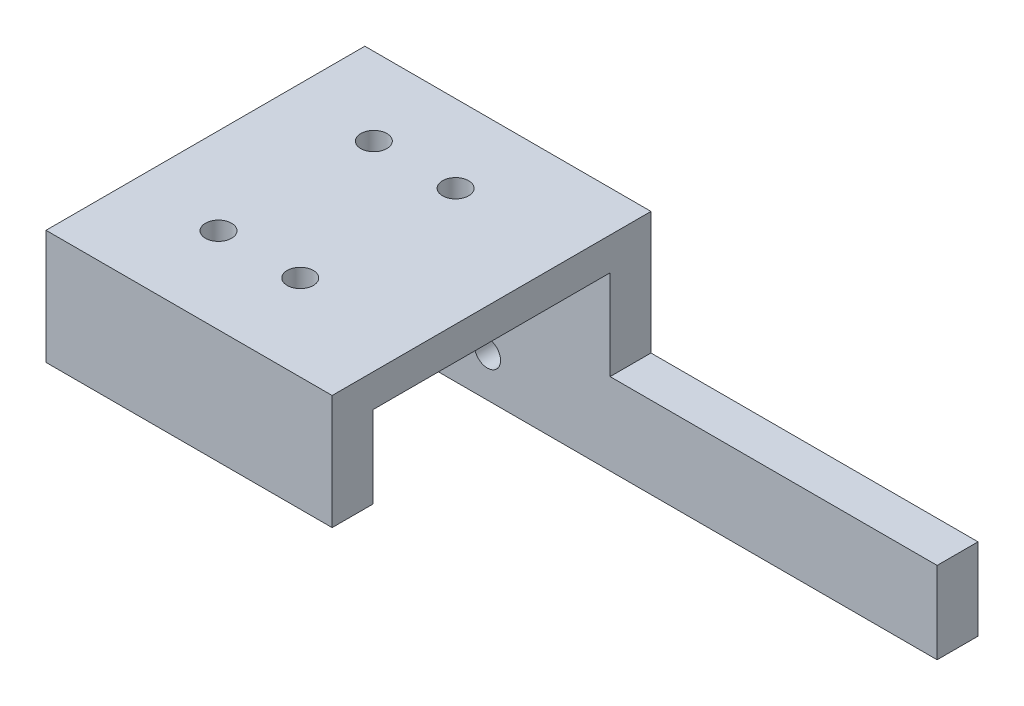
SolidWorks part; units mm, degrees
ref_plane "前视基准面" through (0, 0, 0) normal (0, 0, 1) x (1, 0, 0)
ref_plane "上视基准面" through (0, 0, 0) normal (0, 1, 0) x (1, 0, 0)
ref_plane "右视基准面" through (0, 0, 0) normal (1, 0, 0) x (0, 0, -1)
sketch "草图1" plane through (0, 0, 0) normal (0, 1, 0) x (1, 0, 0)
  line L1 (0, 0) -> (35, 0)
  line L2 (0, 0) -> (0, 39)
  line L3 (0, 39) -> (35, 39)
  line L4 (35, 0) -> (35, 39)
  dimension "D1" = 39
  dimension "D2" = 35
extrude "凸台-拉伸1" add sketch "草图1" along normal blind 4
sketch "草图2" plane through (0, 4, 0) normal (0, 1, 0) x (1, 0, 0)
  line L1 (0, 0) -> (35, 0) construction
  line L3 (0, 20) -> (35, 20) construction
  line L4 (0, 39) -> (0, 0) construction
  circle A0 centre (10.6, 29.5) radius 1.6
  circle A1 centre (20.6, 29.5) radius 1.6
  circle A2 centre (20.6, 10.5) radius 1.6
  circle A3 centre (10.6, 10.5) radius 1.6
  dimension "D3" = 3.2
  dimension "D1" = 10.6
  dimension "D2" = 9.5
  dimension "D4" = 10
  dimension "D5" = 20
extrude "切除-拉伸1" cut sketch "草图2" against normal blind 6
sketch "草图3" plane through (0, 0, 0) normal (0, -1, 0) x (1, 0, 0)
  line L11 (0, -39) -> (35, -39)
  line L12 (0, -39) -> (0, -34)
  line L13 (0, -34) -> (35, -34)
  line L14 (35, -39) -> (35, -34)
  dimension "D1" = 5
  dimension "D2" = 35
extrude "凸台-拉伸2" add sketch "草图3" along normal blind 21
sketch "草图4" plane through (0, 0, -39) normal (0, 0, -1) x (-1, 0, 0)
  line L1 (0, -21) -> (-35, -21) construction
  line L2 (0, 4) -> (0, -21) construction
  circle A0 centre (-10, -16) radius 1.6
  circle A1 centre (-20, -16) radius 1.6
  dimension "D1" = 3.2
  dimension "D4" = 3.2
  dimension "D2" = 10
  dimension "D3" = 5
  dimension "D5" = 5
  dimension "D6" = 10
extrude "切除-拉伸2" cut sketch "草图4" against normal blind 15
sketch "草图5" plane through (0, 0, -39) normal (0, 0, -1) x (-1, 0, 0)
  circle A0 centre (-20, -16) radius 2.8
  circle A1 centre (-10, -16) radius 2.8
  dimension "D1" = 5.6
  dimension "D2" = 5.6
extrude "切除-拉伸3" cut sketch "草图5" against normal blind 2
sketch "草图6" plane through (0, 0, -39) normal (0, 0, -1) x (-1, 0, 0)
  line L1 (-35, -21) -> (-75, -21)
  line L2 (-35, -21) -> (-35, -11)
  line L3 (-35, -11) -> (-75, -11)
  line L4 (-75, -21) -> (-75, -11)
  dimension "D1" = 10
  dimension "D2" = 40
extrude "凸台-拉伸3" add sketch "草图6" against normal blind 5
sketch "草图7" plane through (0, 0, 0) normal (0, -1, 0) x (1, 0, 0)
  line L0 (35, 0) -> (35, -34) construction
  line L1 (0, 0) -> (35, 0)
  line L2 (0, 0) -> (0, -5)
  line L3 (0, -5) -> (35, -5)
  line L4 (35, 0) -> (35, -5)
  dimension "D1" = 5
extrude "凸台-拉伸4" add sketch "草图7" along normal blind 10
equation "\"20、\"=19"
